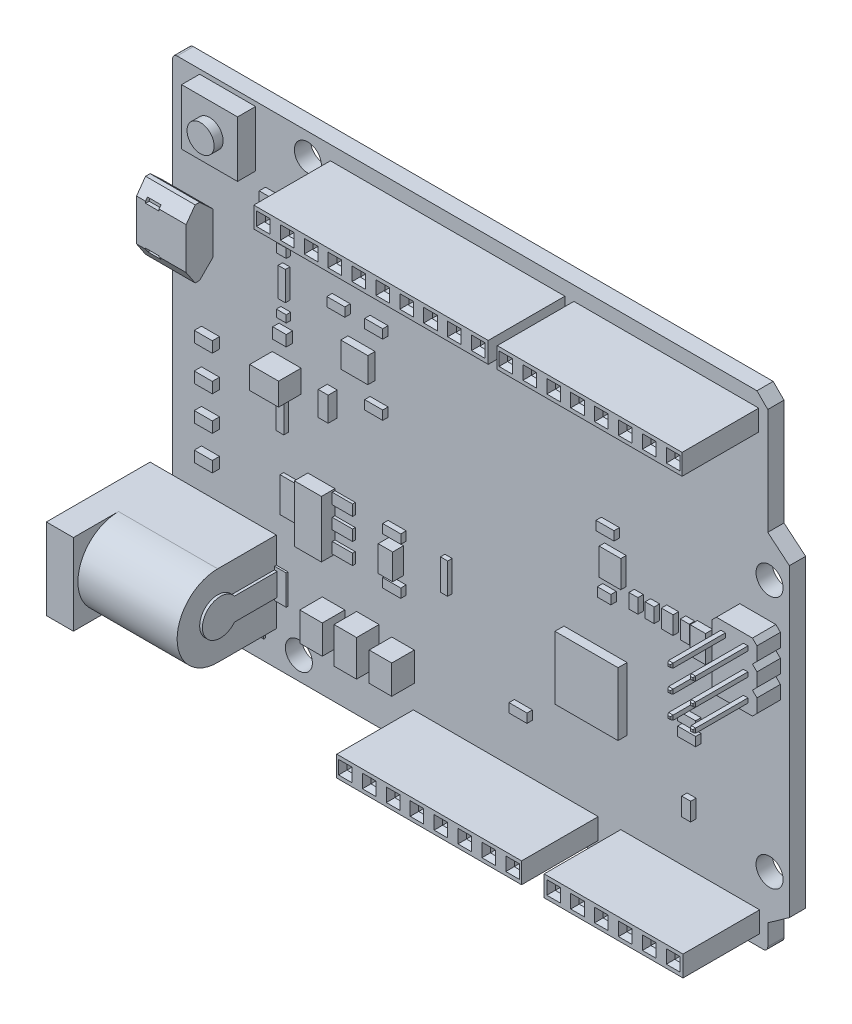
SolidWorks part; units mm, degrees
ref_plane "Front Plane" through (0, 0, 0) normal (0, 0, 1) x (1, 0, 0)
ref_plane "Top Plane" through (0, 0, 0) normal (0, 1, 0) x (1, 0, 0)
ref_plane "Right Plane" through (0, 0, 0) normal (1, 0, 0) x (0, 0, -1)
sketch "Sketch1" plane through (0, 0, 0) normal (0, 0, 1) x (1, 0, 0)
  line L0 (66, -1.2) -> (66, -13)
  line L1 (0.5, 0) -> (64.8, 0)
  line L2 (0, -0.5) -> (0, -52.8)
  line L3 (0.5, -53.3) -> (65.5, -53.3)
  line L4 (68.4, -15) -> (68.4, -48.8)
  line L5 (66, -13) -> (68.4, -15)
  line L6 (68.4, -48.8) -> (66, -50.5)
  line L7 (66, -50.5) -> (66, -52.8)
  line L8 (64.8, 0) -> (66, -1.2)
  arc A0 (65.5, -53.3) -> (66, -52.8) centre (65.5, -52.8) ccw
  arc A1 (0, -52.8) -> (0.5, -53.3) centre (0.5, -52.8) ccw
  arc A2 (0.5, 0) -> (0, -0.5) centre (0.5, -0.5) ccw
  point P12 (66, -53.3)
  point P15 (0, -53.3)
  point P18 (0, 0)
  dimension "D5" = 0.5
  dimension "D1" = 68.4
  dimension "D2" = 53.3
  dimension "D3" = 66
  dimension "D4" = 66
  dimension "D6" = 15
  dimension "D7" = 48.8
  dimension "D8" = 50.5
  dimension "D9" = 45
  dimension "D10" = 1.2
extrude "Boss-Extrude1" add sketch "Sketch1" along normal blind 1.8
sketch "Sketch2" plane through (0, 0, 1.8) normal (0, 0, 1) x (1, 0, 0)
  line L0 (0, -0.5) -> (0, -52.8) construction
  line L1 (64.8, 0) -> (0.5, 0) construction
  line L2 (68.4, -48.8) -> (68.4, -15) construction
  line L3 (0.5, -53.3) -> (65.5, -53.3) construction
  point P0 (15, -2.5)
  point P1 (66.2, -17.5)
  point P2 (66.2, -45.5)
  point P3 (14, -50.8)
  dimension "D1" = 15
  dimension "D2" = 2.5
  dimension "D3" = 2.2
  dimension "D4" = 2.2
  dimension "D5" = 2.5
  dimension "D6" = 14
  dimension "D7" = 17.5
  dimension "D8" = 45.5
hole_wizard "Ø3.0 (3) Diameter Hole2" positions "Sketch6" profile "Sketch7" hole size "Ø3.0" standard "ISO" end condition through all
sketch "Sketch6" plane through (0, 0, 1.8) normal (0, 0, 1) x (1, 0, 0)
  point P0 (15, -2.5)
  point P3 (66.2, -17.5)
  point P6 (66.2, -45.5)
  point P9 (14, -50.8)
sketch "Sketch7" plane through (15, -2.5, 1.8) normal (1, 0, 0) x (0, -1, 0)
  line L0 (0, 0) -> (0, 1.8)
  line L1 (0, 1.8) -> (1.5, 1.8)
  line L2 (1.5, 1.8) -> (1.5, 0)
  line L5 (1.5, 0) -> (0, 0)
  line L11 (0, -6.35) -> (0, 107.95) construction
  dimension "Thru Hole Dia." = 3
  dimension "Thru Hole Depth" = 1.8
sketch "Sketch8" plane through (0, 0, 1.8) normal (0, 0, 1) x (1, 0, 0)
  line L0 (0.5, -53.3) -> (65.5, -53.3) construction
  line L1 (44.5, -1.5683) -> (65, -1.5683)
  line L2 (44.5, -1.5683) -> (44.5, -3.8683)
  line L3 (44.5, -3.8683) -> (65, -3.8683)
  line L4 (65, -1.5683) -> (65, -3.8683)
  line L5 (17.5, -1.5683) -> (43.5, -1.5683)
  line L6 (17.5, -1.5683) -> (17.5, -3.8683)
  line L7 (17.5, -3.8683) -> (43.5, -3.8683)
  line L8 (43.5, -1.5683) -> (43.5, -3.8683)
  line L9 (65.1, -52) -> (49.7, -52)
  line L10 (65.1, -52) -> (65.1, -49.7)
  line L11 (65.1, -49.7) -> (49.7, -49.7)
  line L12 (49.7, -52) -> (49.7, -49.7)
  line L13 (47.2, -52) -> (26.7, -52)
  line L14 (47.2, -52) -> (47.2, -49.7)
  line L15 (47.2, -49.7) -> (26.7, -49.7)
  line L16 (26.7, -52) -> (26.7, -49.7)
  line L17 (68.4, -48.8) -> (68.4, -15) construction
  line L18 (66, -13) -> (66, -1.2) construction
  dimension "D1" = 2.3
  dimension "D2" = 2.3
  dimension "D3" = 2.3
  dimension "D4" = 2.3
  dimension "D5" = 15.4
  dimension "D6" = 1.3
  dimension "D7" = 1.3
  dimension "D8" = 20.5
  dimension "D9" = 2.5
  dimension "D10" = 3.3
  dimension "D11" = 1
  dimension "D12" = 1
  dimension "D13" = 20.5
  dimension "D14" = 26
extrude "Boss-Extrude2" add sketch "Sketch8" along normal blind 8.5
sketch "Sketch10" plane through (0, 0, 10.3) normal (0, 0, 1) x (1, 0, 0)
  line L0 (26.7, -49.7) -> (26.7, -52) construction
  line L1 (26.9, -50.1) -> (28.4, -50.1)
  line L2 (26.9, -50.1) -> (26.9, -51.6)
  line L3 (26.9, -51.6) -> (28.4, -51.6)
  line L4 (28.4, -50.1) -> (28.4, -51.6)
  line L5 (26.7, -52) -> (47.2, -52) construction
  dimension "D1" = 1.5
  dimension "D2" = 1.5
  dimension "D3" = 0.2
  dimension "D4" = 0.4
extrude "Cut-Extrude1" cut sketch "Sketch10" against normal blind 8.5 draft 20
sketch "Sketch11" plane through (0, 0, 10.3) normal (0, 0, 1) x (1, 0, 0)
  line L0 (27.65, -50.85) -> (28.4, -51.6) construction
  line L1 (27.15, -50.35) -> (28.15, -50.35)
  line L2 (27.15, -50.35) -> (27.15, -51.35)
  line L3 (27.15, -51.35) -> (28.15, -51.35)
  line L4 (28.15, -50.35) -> (28.15, -51.35)
  line L5 (27.15, -50.35) -> (28.15, -51.35) construction
  line L6 (27.15, -51.35) -> (28.15, -50.35) construction
  point P0 (27.65, -50.85)
  dimension "D1" = 1
  dimension "D2" = 1
extrude "Cut-Extrude2" cut sketch "Sketch11" against normal blind 8.5
pattern_linear "LPattern1" count 8 spacing 2.65 along (1, 0, 0) of "Cut-Extrude2", "Cut-Extrude1"
sketch "Sketch12" plane through (0, 0, 10.3) normal (0, 0, 1) x (1, 0, 0)
  line L0 (65.1, -49.7) -> (49.7, -49.7) construction
  line L1 (50, -50.1) -> (51.5, -50.1)
  line L2 (50, -50.1) -> (50, -51.6)
  line L3 (50, -51.6) -> (51.5, -51.6)
  line L4 (51.5, -50.1) -> (51.5, -51.6)
  line L5 (49.7, -49.7) -> (49.7, -52) construction
  dimension "D1" = 1.5
  dimension "D2" = 1.5
  dimension "D3" = 0.4
  dimension "D4" = 0.3
extrude "Cut-Extrude3" cut sketch "Sketch12" against normal blind 8.5 draft 20
sketch "Sketch14" plane through (0, 0, 10.3) normal (0, 0, 1) x (1, 0, 0)
  line L0 (50.75, -50.85) -> (51.5, -50.1) construction
  line L1 (50.25, -50.35) -> (51.25, -50.35)
  line L2 (50.25, -50.35) -> (50.25, -51.35)
  line L3 (50.25, -51.35) -> (51.25, -51.35)
  line L4 (51.25, -50.35) -> (51.25, -51.35)
  line L5 (50.25, -50.35) -> (51.25, -51.35) construction
  line L6 (50.25, -51.35) -> (51.25, -50.35) construction
  line L7 (50.75, -50.85) -> (50, -51.6) construction
  line L8 (51.5, -50.1) -> (50, -50.1) construction
  line L9 (50, -50.1) -> (50, -51.6) construction
  point P0 (50.75, -50.85)
  dimension "D1" = 1
  dimension "D2" = 1
  dimension "D3" = 0.25
  dimension "D4" = 0.25
extrude "Cut-Extrude4" cut sketch "Sketch14" against normal blind 8.5
pattern_linear "LPattern2" count 6 spacing 2.65 along (1, 0, 0) of "Cut-Extrude4", "Cut-Extrude3"
sketch "Sketch15" plane through (0, 0, 10.3) normal (0, 0, 1) x (1, 0, 0)
  line L0 (17.5, -1.5683) -> (17.5, -3.8683) construction
  line L1 (17.8, -1.9683) -> (19.3, -1.9683)
  line L2 (17.8, -1.9683) -> (17.8, -3.4683)
  line L3 (17.8, -3.4683) -> (19.3, -3.4683)
  line L4 (19.3, -1.9683) -> (19.3, -3.4683)
  line L5 (43.5, -1.5683) -> (17.5, -1.5683) construction
  point P4 (17.5, -2.7183)
  dimension "D1" = 0.3
  dimension "D2" = 1.5
  dimension "D3" = 0.4
  dimension "D4" = 1.5
extrude "Cut-Extrude5" cut sketch "Sketch15" against normal blind 8.5 draft 20
sketch "Sketch16" plane through (0, 0, 10.3) normal (0, 0, 1) x (1, 0, 0)
  line L0 (18.55, -2.7183) -> (19.3, -3.4683) construction
  line L1 (18.0652, -2.2335) -> (19.0652, -2.2335)
  line L2 (18.0652, -2.2335) -> (18.0652, -3.2335)
  line L3 (18.0652, -3.2335) -> (19.0652, -3.2335)
  line L4 (19.0652, -2.2335) -> (19.0652, -3.2335)
  line L5 (18.0652, -2.2335) -> (19.0652, -3.2335) construction
  line L6 (18.0652, -3.2335) -> (19.0652, -2.2335) construction
  point P0 (18.5652, -2.7335)
  dimension "D1" = 1
extrude "Cut-Extrude6" cut sketch "Sketch16" against normal blind 8.5
pattern_linear "LPattern3" count 10 spacing 2.65 along (1, 0, 0) of "Cut-Extrude5", "Cut-Extrude6"
sketch "Sketch17" plane through (0, 0, 10.3) normal (0, 0, 1) x (1, 0, 0)
  line L0 (65, -1.5683) -> (44.5, -1.5683) construction
  line L1 (44.7, -1.9683) -> (46.2, -1.9683)
  line L2 (44.7, -1.9683) -> (44.7, -3.4683)
  line L3 (44.7, -3.4683) -> (46.2, -3.4683)
  line L4 (46.2, -1.9683) -> (46.2, -3.4683)
  line L5 (44.5, -1.5683) -> (44.5, -3.8683) construction
  dimension "D1" = 0.4
  dimension "D2" = 1.5
  dimension "D3" = 1.5
  dimension "D4" = 0.2
extrude "Cut-Extrude7" cut sketch "Sketch17" against normal blind 8.5 draft 20
sketch "Sketch18" plane through (0, 0, 10.3) normal (0, 0, 1) x (1, 0, 0)
  line L0 (45.45, -2.7183) -> (46.2, -3.4683) construction
  line L1 (44.95, -2.2183) -> (45.95, -2.2183)
  line L2 (44.95, -2.2183) -> (44.95, -3.2183)
  line L3 (44.95, -3.2183) -> (45.95, -3.2183)
  line L4 (45.95, -2.2183) -> (45.95, -3.2183)
  line L5 (44.95, -2.2183) -> (45.95, -3.2183) construction
  line L6 (44.95, -3.2183) -> (45.95, -2.2183) construction
  point P0 (45.45, -2.7183)
  dimension "D1" = 1
extrude "Cut-Extrude8" cut sketch "Sketch18" against normal blind 8.5
pattern_linear "LPattern4" count 8 spacing 2.65 along (1, 0, 0) of "Cut-Extrude8", "Cut-Extrude7"
sketch "Sketch19" plane through (0, 0, 1.8) normal (0, 0, 1) x (1, 0, 0)
  line L0 (68.4, -48.8) -> (68.4, -15) construction
  line L1 (62.4, -21.4) -> (67.4, -21.4)
  line L2 (62.4, -21.4) -> (62.4, -23.4)
  line L3 (62.4, -28.9) -> (67.4, -28.9)
  line L4 (67.4, -21.4) -> (67.4, -23.4)
  line L5 (64.8, 0) -> (0.5, 0) construction
  line L6 (66.9, -26.4) -> (67.4, -25.9)
  line L7 (66.9, -26.4) -> (67.4, -26.9)
  line L10 (62.9, -26.4) -> (62.4, -26.9)
  line L11 (62.9, -26.4) -> (62.4, -25.9)
  line L12 (66.9, -23.9) -> (67.4, -23.4)
  line L13 (66.9, -23.9) -> (67.4, -24.4)
  line L14 (62.9, -23.9) -> (62.4, -24.4)
  line L15 (62.9, -23.9) -> (62.4, -23.4)
  line L16 (62.4, -24.4) -> (62.4, -25.9)
  line L17 (62.4, -26.9) -> (62.4, -28.9)
  line L18 (67.4, -24.4) -> (67.4, -25.9)
  line L19 (67.4, -26.9) -> (67.4, -28.9)
  dimension "D1" = 5
  dimension "D2" = 7.5
  dimension "D3" = 5
  dimension "D4" = 1
  dimension "D5" = 21.4
  dimension "D6" = 2.5
  dimension "D7" = 5
  dimension "D8" = 90
  dimension "D9" = 135
  dimension "D10" = 135
  dimension "D11" = 90
  dimension "D12" = 90
  dimension "D13" = 90
  dimension "D14" = 135
  dimension "D15" = 135
  dimension "D16" = 0.5
  dimension "D17" = 0.5
  dimension "D18" = 0.5
  dimension "D19" = 0.5
extrude "Boss-Extrude3" add sketch "Sketch19" along normal blind 2.6
chamfer "Chamfer1" distance 0.5 angle 45 4 edges at (62.4, -21.4, 3.1) (62.4, -28.9, 3.1) (67.4, -28.9, 3.1) (67.4, -21.4, 3.1)
sketch "Sketch20" plane through (0, 0, 4.4) normal (0, 0, 1) x (1, 0, 0)
  line L0 (66.9, -21.4) -> (62.9, -21.4) construction
  line L1 (63.4, -22.4) -> (63.9, -22.4)
  line L2 (63.4, -22.4) -> (63.4, -22.9)
  line L3 (63.4, -22.9) -> (63.9, -22.9)
  line L4 (63.9, -22.4) -> (63.9, -22.9)
  line L5 (65.9, -22.4) -> (66.4, -22.4)
  line L6 (65.9, -22.4) -> (65.9, -22.9)
  line L7 (65.9, -22.9) -> (66.4, -22.9)
  line L8 (66.4, -22.4) -> (66.4, -22.9)
  line L9 (62.4, -21.9) -> (62.4, -23.4) construction
  line L10 (67.4, -23.4) -> (67.4, -21.9) construction
  point P11 (62.4, -22.65)
  dimension "D1" = 0.5
  dimension "D2" = 0.5
  dimension "D3" = 0.5
  dimension "D4" = 0.5
  dimension "D5" = 2
  dimension "D6" = 1
  dimension "D7" = 1
  dimension "D8" = 1
  dimension "D9" = 1
  dimension "D10" = 1
extrude "Boss-Extrude4" add sketch "Sketch20" along normal blind 6
chamfer "Chamfer2" distance 0.2 angle 30 8 edges at (66.4, -22.65, 10.4) (66.15, -22.9, 10.4) (65.9, -22.65, 10.4) (66.15, -22.4, 10.4) (63.9, -22.65, 10.4) (63.65, -22.4, 10.4) (63.4, -22.65, 10.4) (63.65, -22.9, 10.4) first distance on face at (66.4, -22.65, 7.4) first distance on face at (66.15, -22.9, 7.4) first distance on face at (65.9, -22.65, 7.4) first distance on face at (66.15, -22.4, 7.4) first distance on face at (63.9, -22.65, 7.4) first distance on face at (63.65, -22.4, 7.4) first distance on face at (63.4, -22.65, 7.4) first distance on face at (63.65, -22.9, 7.4)
pattern_linear "LPattern6" count 3 spacing 2.5 along (0, -1, 0) of "Chamfer2", "Boss-Extrude4"
sketch "Sketch21" plane through (0, 0, 1.8) normal (0, 0, 1) x (1, 0, 0)
  line L0 (68.4, -48.8) -> (68.4, -15) construction
  line L1 (43.4, -33.3) -> (50.4, -33.3)
  line L2 (43.4, -33.3) -> (43.4, -40.3)
  line L3 (43.4, -40.3) -> (50.4, -40.3)
  line L4 (50.4, -33.3) -> (50.4, -40.3)
  line L5 (0.5, -53.3) -> (65.5, -53.3) construction
  dimension "D1" = 7
  dimension "D2" = 7
  dimension "D3" = 18
  dimension "D4" = 20
extrude "Boss-Extrude5" add sketch "Sketch21" along normal blind 1
sketch "Sketch22" plane through (0, 0, 1.8) normal (0, 0, 1) x (1, 0, 0)
  line L0 (62.4, -26.9) -> (62.4, -28.4) construction
  line L1 (58.2, -25.3683) -> (59.9, -25.3683)
  line L2 (58.2, -25.3683) -> (58.2, -28.3683)
  line L3 (58.2, -28.3683) -> (59.9, -28.3683)
  line L4 (59.9, -25.3683) -> (59.9, -28.3683)
  line L5 (44.5, -3.8683) -> (65, -3.8683) construction
  point P4 (62.4, -27.65)
  dimension "D1" = 3
  dimension "D2" = 1.7
  dimension "D3" = 2.5
  dimension "D4" = 21.5
extrude "Boss-Extrude6" add sketch "Sketch22" along normal blind 0.8
sketch "Sketch23" plane through (0, 0, 1.8) normal (0, 0, 1) x (1, 0, 0)
  line L0 (58.2, -25.3683) -> (58.2, -28.3683) construction
  line L1 (56.9, -25.5683) -> (57.9, -25.5683)
  line L2 (56.9, -25.5683) -> (56.9, -27.5683)
  line L3 (56.9, -27.5683) -> (57.9, -27.5683)
  line L4 (57.9, -25.5683) -> (57.9, -27.5683)
  line L5 (54.8, -25.5683) -> (56.1, -25.5683)
  line L6 (54.8, -25.5683) -> (54.8, -27.5683)
  line L7 (54.8, -27.5683) -> (56.1, -27.5683)
  line L8 (56.1, -25.5683) -> (56.1, -27.5683)
  line L10 (53, -25.8683) -> (54, -25.8683)
  line L11 (53, -25.8683) -> (53, -27.4683)
  line L12 (53, -27.4683) -> (54, -27.4683)
  line L13 (51.2, -25.8683) -> (52.2, -25.8683)
  line L14 (51.2, -25.8683) -> (51.2, -27.4683)
  line L15 (51.2, -27.4683) -> (52.2, -27.4683)
  line L16 (52.2, -25.8683) -> (52.2, -27.4683)
  line L17 (47.9, -23.0683) -> (50.3, -23.0683)
  line L18 (47.9, -23.0683) -> (47.9, -26.0683)
  line L19 (47.9, -26.0683) -> (50.3, -26.0683)
  line L20 (50.3, -23.0683) -> (50.3, -26.0683)
  line L21 (47.5517, -20.7683) -> (49.5517, -20.7683)
  line L22 (47.5517, -20.7683) -> (47.5517, -21.7683)
  line L23 (47.5517, -21.7683) -> (49.5517, -21.7683)
  line L24 (49.5517, -20.7683) -> (49.5517, -21.7683)
  line L25 (47.7, -27.0683) -> (49.2, -27.0683)
  line L26 (47.7, -27.0683) -> (47.7, -28.0683)
  line L27 (47.7, -28.0683) -> (49.2, -28.0683)
  line L28 (49.2, -27.0683) -> (49.2, -28.0683)
  line L29 (59.9, -25.3683) -> (58.2, -25.3683) construction
  line L30 (54, -25.8683) -> (54, -27.4683)
  dimension "D1" = 0.3
  dimension "D2" = 1
  dimension "D3" = 1.3
  dimension "D4" = 1
  dimension "D5" = 1
  dimension "D6" = 0.2
  dimension "D7" = 0.8
  dimension "D8" = 0.8
  dimension "D9" = 0.8
  dimension "D10" = 0.3
  dimension "D11" = 1.6
  dimension "D12" = 1.6
  dimension "D13" = 0.3
  dimension "D14" = 2
  dimension "D15" = 2
  dimension "D16" = 2.4
  dimension "D17" = 0.9
  dimension "D18" = 3
  dimension "D19" = 0.2
  dimension "D20" = 1
  dimension "D21" = 1.5
  dimension "D22" = 2
  dimension "D23" = 1
  dimension "D24" = 2
  dimension "D25" = 1.3
  dimension "D26" = 1
extrude "Boss-Extrude7" add sketch "Sketch23" along normal blind 0.6
sketch "Sketch24" plane through (0, 0, 1.8) normal (0, 0, 1) x (1, 0, 0)
  line L0 (65.1, -49.7) -> (49.7, -49.7) construction
  line L1 (56.6, -34.5) -> (58.6, -34.5)
  line L2 (56.6, -34.5) -> (56.6, -35.5)
  line L3 (56.6, -35.5) -> (58.6, -35.5)
  line L4 (58.6, -34.5) -> (58.6, -35.5)
  line L5 (56.6, -36) -> (58.6, -36)
  line L6 (56.6, -36) -> (56.6, -37)
  line L7 (56.6, -37) -> (58.6, -37)
  line L8 (58.6, -36) -> (58.6, -37)
  line L9 (57.0515, -42.5) -> (58.0515, -42.5)
  line L10 (57.0515, -42.5) -> (57.0515, -44.5)
  line L11 (57.0515, -44.5) -> (58.0515, -44.5)
  line L12 (58.0515, -42.5) -> (58.0515, -44.5)
  line L13 (37.9, -43.1) -> (39.9, -43.1)
  line L14 (37.9, -43.1) -> (37.9, -44.1)
  line L15 (37.9, -44.1) -> (39.9, -44.1)
  line L16 (39.9, -43.1) -> (39.9, -44.1)
  line L17 (21.9, -22) -> (23.9, -22)
  line L18 (21.9, -22) -> (21.9, -23)
  line L19 (21.9, -23) -> (23.9, -23)
  line L20 (23.9, -22) -> (23.9, -23)
  line L21 (23.9, -32.9) -> (25.9, -32.9)
  line L22 (23.9, -32.9) -> (23.9, -33.9)
  line L23 (23.9, -33.9) -> (25.9, -33.9)
  line L24 (25.9, -32.9) -> (25.9, -33.9)
  line L25 (23.9, -38.1) -> (25.9, -38.1)
  line L26 (23.9, -38.1) -> (23.9, -39.1)
  line L27 (23.9, -39.1) -> (25.9, -39.1)
  line L28 (25.9, -38.1) -> (25.9, -39.1)
  line L29 (50.4, -40.3) -> (50.4, -33.3) construction
  line L30 (43.4, -33.3) -> (43.4, -40.3) construction
  line L31 (47.2, -49.7) -> (26.7, -49.7) construction
  line L33 (43.4, -33.3) -> (43.4, -40.3) construction
  line L34 (17.7, -14.2) -> (19.7, -14.2)
  line L35 (17.7, -14.2) -> (17.7, -15.2)
  line L36 (17.7, -15.2) -> (19.7, -15.2)
  line L37 (19.7, -14.2) -> (19.7, -15.2)
  line L38 (21.9, -14.2) -> (23.9, -14.2)
  line L39 (21.9, -14.2) -> (21.9, -15.2)
  line L40 (21.9, -15.2) -> (23.9, -15.2)
  line L41 (23.9, -14.2) -> (23.9, -15.2)
  dimension "D1" = 1
  dimension "D2" = 1
  dimension "D3" = 2
  dimension "D4" = 2
  dimension "D5" = 1
  dimension "D6" = 2
  dimension "D7" = 1
  dimension "D8" = 1
  dimension "D9" = 2
  dimension "D10" = 2
  dimension "D11" = 2
  dimension "D12" = 1
  dimension "D13" = 2
  dimension "D14" = 1
  dimension "D15" = 5.2
  dimension "D16" = 5.5
  dimension "D17" = 0.5
  dimension "D18" = 6.2
  dimension "D19" = 3.5
  dimension "D20" = 5.6
  dimension "D21" = 10.6
  dimension "D22" = 4.2
  dimension "D23" = 17.5
  dimension "D24" = 19.5
  dimension "D25" = 9.9
  dimension "D26" = 2
  dimension "D27" = 2
  dimension "D28" = 2.2
  dimension "D29" = 19.5
  dimension "D30" = 6.8
  dimension "D31" = 6.8
  dimension "D32" = 1
  dimension "D33" = 1
  dimension "D34" = 17.5
extrude "Boss-Extrude8" add sketch "Sketch24" along normal blind 0.6
sketch "Sketch25" plane through (0, 0, 1.8) normal (0, 0, 1) x (1, 0, 0)
  line L0 (17.7, -15.2) -> (19.7, -15.2) construction
  line L1 (19.45, -17.4) -> (22.45, -17.4)
  line L2 (19.45, -17.4) -> (19.45, -20.2)
  line L3 (19.45, -20.2) -> (22.45, -20.2)
  line L4 (22.45, -17.4) -> (22.45, -20.2)
  line L5 (23.9, -23) -> (23.9, -22) construction
  dimension "D1" = 2.2
  dimension "D2" = 2.8
  dimension "D3" = 3
  dimension "D4" = 1.45
extrude "Boss-Extrude9" add sketch "Sketch25" along normal blind 0.8
sketch "Sketch26" plane through (0, 0, 1.8) normal (0, 0, 1) x (1, 0, 0)
  line L0 (25.9, -38.1) -> (23.9, -38.1) construction
  line L1 (24, -34.4854) -> (25.6, -34.4854)
  line L2 (24, -34.4854) -> (24, -37.35)
  line L3 (24, -37.35) -> (25.6, -37.35)
  line L4 (25.6, -34.4854) -> (25.6, -37.35)
  line L5 (43.4, -33.3) -> (43.4, -40.3) construction
  dimension "D1" = 1.6
  dimension "D2" = 2.8646
  dimension "D3" = 0.75
  dimension "D4" = 17.8
extrude "Boss-Extrude10" add sketch "Sketch26" along normal blind 1.2
sketch "Sketch27" plane through (0, 0, 1.8) normal (0, 0, 1) x (1, 0, 0)
  line L0 (43.4, -33.3) -> (43.4, -40.3) construction
  line L1 (24.3, -44.5) -> (26.8, -44.5)
  line L2 (24.3, -44.5) -> (24.3, -46.5)
  line L3 (24.3, -46.5) -> (26.8, -46.5)
  line L4 (26.8, -44.5) -> (26.8, -46.5)
  line L5 (16.6, -44.5) -> (19.1, -44.5)
  line L6 (16.6, -44.5) -> (16.6, -46.5)
  line L7 (16.6, -46.5) -> (19.1, -46.5)
  line L8 (19.1, -44.5) -> (19.1, -46.5)
  line L9 (20.4, -43.4) -> (22.9, -43.4)
  line L10 (20.4, -43.4) -> (20.4, -47.4)
  line L11 (20.4, -47.4) -> (22.9, -47.4)
  line L12 (22.9, -43.4) -> (22.9, -47.4)
  line L13 (47.2, -49.7) -> (26.7, -49.7) construction
  line L14 (47.2, -49.7) -> (26.7, -49.7) construction
  dimension "D1" = 2.5
  dimension "D2" = 2.5
  dimension "D3" = 2
  dimension "D4" = 2
  dimension "D5" = 16.6
  dimension "D6" = 5.2
  dimension "D7" = 3.2
  dimension "D8" = 2.3
  dimension "D9" = 2.5
  dimension "D10" = 4
  dimension "D11" = 1.4
extrude "Boss-Extrude11" add sketch "Sketch27" along normal blind 2.5
sketch "Sketch28" plane through (0, 0, 1.8) normal (0, 0, 1) x (1, 0, 0)
  line L1 (24.3, -44.5) -> (26.8, -44.5)
  line L2 (24.3, -44.5) -> (24.3, -43.9)
  line L3 (24.3, -43.9) -> (26.8, -43.9)
  line L4 (26.8, -44.5) -> (26.8, -43.9)
  line L5 (24.3, -46.5) -> (26.8, -46.5)
  line L6 (24.3, -46.5) -> (24.3, -47.1)
  line L7 (24.3, -47.1) -> (26.8, -47.1)
  line L8 (26.8, -46.5) -> (26.8, -47.1)
  line L9 (19.1, -46.5) -> (16.6, -46.5)
  line L10 (19.1, -46.5) -> (19.1, -47.1)
  line L11 (19.1, -47.1) -> (16.6, -47.1)
  line L12 (16.6, -46.5) -> (16.6, -47.1)
  line L13 (16.6, -44.5) -> (19.1, -44.5)
  line L14 (16.6, -44.5) -> (16.6, -43.9)
  line L15 (16.6, -43.9) -> (19.1, -43.9)
  line L16 (19.1, -44.5) -> (19.1, -43.9)
  dimension "D1" = 0.6
  dimension "D2" = 0.6
  dimension "D5" = 0.6
  dimension "D6" = 0.6
extrude "Boss-Extrude12" add sketch "Sketch28" along normal blind 2.5
sketch "Sketch30" plane through (0, 0, 1.8) normal (0, 0, 1) x (1, 0, 0)
  line L0 (0.5, -53.3) -> (65.5, -53.3) construction
  line L1 (11.5, -40.5) -> (-2.5, -40.5)
  line L2 (11.5, -40.5) -> (11.5, -49.5)
  line L3 (11.5, -49.5) -> (-2.5, -49.5)
  line L4 (-2.5, -40.5) -> (-2.5, -49.5)
  line L5 (0, -0.5) -> (0, -52.8) construction
  dimension "D1" = 14
  dimension "D2" = 9
  dimension "D3" = 3.8
  dimension "D4" = 2.5
extrude "Boss-Extrude13" add sketch "Sketch30" along normal blind 6.5
sketch "Sketch31" plane through (-2.5, 0, 0) normal (-1, 0, 0) x (0, 0, 1)
  line L0 (8.3, -40.5) -> (8.3, -49.5) construction
  circle A0 centre (8.3, -45) radius 4.5
  dimension "D1" = 9
extrude "Boss-Extrude14" add sketch "Sketch31" against normal blind 14
sketch "Sketch32" plane through (-2.5, 0, 0) normal (-1, 0, 0) x (0, 0, 1)
  line L1 (8.3, -40.5) -> (13.3, -40.5)
  line L2 (8.3, -40.5) -> (8.3, -49.5)
  line L3 (8.3, -49.5) -> (13.3, -49.5)
  line L4 (13.3, -40.5) -> (13.3, -49.5)
  dimension "D1" = 5
extrude "Boss-Extrude15" add sketch "Sketch32" against normal blind 3
sketch "Sketch33" plane through (-2.5, 0, 0) normal (-1, 0, 0) x (0, 0, 1)
  line L0 (13.3, -49.5) -> (1.8, -49.5) construction
  line L1 (13.3, -49.5) -> (13.3, -40.5) construction
  circle A0 centre (8.3, -45) radius 2.8159
  dimension "D1" = 4.5
  dimension "D2" = 5
extrude "Cut-Extrude9" cut sketch "Sketch33" against normal blind 10
sketch "Sketch34" plane through (7.5, 0, 0) normal (-1, 0, 0) x (0, 0, 1)
  circle A0 centre (8.3, -45) radius 1.25
  dimension "D1" = 2.5
extrude "Boss-Extrude16" add sketch "Sketch34" along normal blind 9
fillet "Fillet1" radius 1.25 1 edges at (-1.5, -46.25, 8.3)
sketch "Sketch35" plane through (0, -49.5, 0) normal (0, -1, 0) x (1, 0, 0)
  line L0 (0, 1.8) -> (11.5, 1.8) construction
  line L1 (7.5, 1.8) -> (10, 1.8)
  line L2 (7.5, 1.8) -> (7.5, 6.3)
  line L3 (7.5, 6.3) -> (10, 6.3)
  line L4 (10, 1.8) -> (10, 6.3)
  line L5 (11.5, 8.3) -> (11.5, 1.8) construction
  dimension "D1" = 2.5
  dimension "D2" = 4.5
  dimension "D3" = 1.5
extrude "Boss-Extrude17" add sketch "Sketch35" along normal blind 0.2
sketch "Sketch36" plane through (11.5, 0, 0) normal (1, 0, 0) x (0, 0, -1)
  line L0 (-1.8, -49.5) -> (-1.8, -40.5) construction
  line L1 (-6.7388, -46.25) -> (-1.8, -46.25)
  line L3 (-6.7388, -43.75) -> (-1.8, -43.75)
  line L4 (-1.8, -46.25) -> (-1.8, -43.75)
  line L5 (-8.3, -40.5) -> (-1.8, -40.5) construction
  line L6 (-1.8, -49.5) -> (-6.3, -49.5) construction
  arc A0 (-6.7388, -43.75) -> (-6.7388, -46.25) centre (-8.3, -45) ccw
  dimension "D2" = 4
  dimension "D1" = 2.5
  dimension "D3" = 3.25
  dimension "D4" = 3.25
extrude "Boss-Extrude18" add sketch "Sketch36" along normal blind 0.3
sketch "Sketch37" plane through (0, 0, 0) normal (-1, 0, 0) x (0, 0, 1)
  line L0 (1.8, -12.7) -> (3.3, -11.3)
  line L2 (1.8, -0.5) -> (1.8, -40.5) construction
  line L3 (3.3, -11.3) -> (3.8, -11.3)
  line L4 (3.8, -11.3) -> (4.8, -12.7)
  line L5 (4.8, -12.7) -> (4.8, -17.3)
  line L6 (3.3, -11.3) -> (3.3, -18.8)
  line L7 (3.3, -18.8) -> (1.8, -17.3)
  line L8 (3.3, -18.8) -> (3.8, -18.8)
  line L9 (3.8, -18.8) -> (4.8, -17.3)
  line L10 (1.8, -12.7) -> (1.8, -17.3)
  line L11 (3.4577, -11.7) -> (3.5942, -11.7)
  line L12 (3.5942, -11.7) -> (4.4, -12.8282)
  line L13 (4.4, -12.8282) -> (4.4, -17.1789)
  line L14 (3.5859, -18.4) -> (4.4, -17.1789)
  line L15 (3.4657, -18.4) -> (3.5859, -18.4)
  line L16 (3.4657, -18.4) -> (2.2, -17.1343)
  line L17 (2.2, -12.8738) -> (2.2, -17.1343)
  line L18 (2.2, -12.8738) -> (3.4577, -11.7)
  line L19 (1.8, 0) -> (0, 0) construction
  line L20 (2.2, -12.8738) -> (3.5729, -11.5924) construction
  line L21 (3.3, -11.7) -> (3.5942, -11.7) construction
  line L22 (3.3, -18.4) -> (3.5859, -18.4) construction
  line L23 (3.5828, -18.5172) -> (2.2, -17.1343) construction
  line M5 (1.8, -40.5) -> (1.8, -0.5)
  dimension "D1" = 3
  dimension "D2" = 1.5
  dimension "D3" = 0.5
  dimension "D4" = 7.5
  dimension "D5" = 1.4
  dimension "D6" = 0.4
  dimension "D7" = 11.3
extrude "Boss-Extrude19" add sketch "Sketch37" against normal blind 4.5 and the other way blind 1 contours L6 L18 L11 L12 L13 L14 L15 L16 L8 L9 L5 L4 L3 | L17 L18 L6 L0 L7 L16 M5 region at (0, -12.0559, 2.6022) region at (0, -11.3765, 3.55)
sketch "Sketch38" plane through (4.5, 0, 0) normal (1, 0, 0) x (0, 0, -1)
  line L0 (-4.4, -12.8282) -> (-4.4, -17.1789)
  line L1 (-4.4, -17.1789) -> (-3.5921, -18.5321)
  line L2 (-3.5921, -18.5321) -> (-3.2472, -18.5321)
  line L3 (-3.2472, -18.5321) -> (-1.9826, -17.1789)
  line L4 (-1.9826, -17.1789) -> (-1.9826, -12.8282)
  line L5 (-1.9826, -12.8282) -> (-3.4766, -11.5142)
  line L6 (-3.4766, -11.5142) -> (-3.7841, -11.5339)
  line L7 (-3.7841, -11.5339) -> (-4.5864, -12.9086)
  line L8 (-4.5864, -12.9086) -> (-4.4, -17.1789)
  line M1 (-2.2, -12.8738) -> (-2.2, -17.1343)
  line M2 (-2.2, -17.1343) -> (-3.4657, -18.4)
  line M3 (-3.4657, -18.4) -> (-3.5859, -18.4)
  line M4 (-3.5859, -18.4) -> (-4.4, -17.1789)
  line M5 (-4.4, -17.1789) -> (-4.4, -12.8282)
  line M6 (-4.4, -12.8282) -> (-3.5942, -11.7)
  line M7 (-3.5942, -11.7) -> (-3.4577, -11.7)
  line M8 (-3.4577, -11.7) -> (-2.2, -12.8738)
extrude "Boss-Extrude20" add sketch "Sketch38" against normal blind 1 contours M1 M8 M7 M6 M5 M4 M3 M2 region at (4.5, -15.0278, 3.3209)
sketch "Sketch39" plane through (3.5, 0, 0) normal (-1, 0, 0) x (0, 0, 1)
  line L0 (4.4, -12.8282) -> (4.4, -17.1789) construction
  line L1 (3.9, -13.0032) -> (3.4, -13.0032)
  line L2 (3.9, -13.0032) -> (3.9, -17.0032)
  line L3 (3.9, -17.0032) -> (3.4, -17.0032)
  line L4 (3.4, -13.0032) -> (3.4, -17.0032)
  dimension "D1" = 0.5
  dimension "D2" = 0.5
  dimension "D3" = 4
  dimension "D4" = 0.175
  dimension "D5" = 0.1757
extrude "Boss-Extrude21" add sketch "Sketch39" along normal blind 4
sketch "Sketch41" plane through (0, 0, 4.8) normal (0, 0, 1) x (1, 0, 0)
  line L0 (-1, -11.3) -> (4.5, -11.3) construction
  line L1 (0, -12.4) -> (1.5, -12.4)
  line L2 (0, -12.4) -> (0, -12.9)
  line L3 (0, -12.9) -> (1.5, -12.9)
  line L4 (1.5, -12.4) -> (1.5, -12.9)
  line L5 (0, -17.2) -> (1.5, -17.2)
  line L6 (0, -17.2) -> (0, -17.7)
  line L7 (0, -17.7) -> (1.5, -17.7)
  line L8 (1.5, -17.2) -> (1.5, -17.7)
  line L9 (-1, -18.8) -> (4.5, -18.8) construction
  line L10 (-1, -11.3) -> (-1, -12.7) construction
  line L11 (-1, -12.7) -> (-1, -17.3) construction
  dimension "D1" = 1.1
  dimension "D2" = 0.5
  dimension "D3" = 0.5
  dimension "D4" = 1.1
  dimension "D5" = 1.5
  dimension "D6" = 1.5
  dimension "D7" = 1
  dimension "D8" = 1
extrude "Cut-Extrude10" cut sketch "Sketch41" against normal blind 1
sketch "Sketch43" plane through (0, 0, 1.8) normal (0, 0, 1) x (1, 0, 0)
  line L0 (64.8, 0) -> (0.5, 0) construction
  line L1 (3, -0.5) -> (9.2, -0.5)
  line L2 (3, -0.5) -> (3, -6.7)
  line L3 (3, -6.7) -> (9.2, -6.7)
  line L4 (9.2, -0.5) -> (9.2, -6.7)
  line L5 (0, -0.5) -> (0, -12.7) construction
  dimension "D1" = 6.2
  dimension "D2" = 6.2
  dimension "D3" = 0.5
  dimension "D4" = 3
extrude "Boss-Extrude22" add sketch "Sketch43" along normal blind 2
sketch "Sketch44" plane through (0, 0, 3.8) normal (0, 0, 1) x (1, 0, 0)
  line L0 (3, -0.5) -> (3, -6.7) construction
  line L1 (9.2, -0.5) -> (3, -0.5) construction
  circle A0 centre (6.1, -3.6) radius 1.5
  dimension "D3" = 3
  dimension "D1" = 3.1
  dimension "D2" = 3.1
extrude "Boss-Extrude23" add sketch "Sketch44" along normal blind 1
sketch "Sketch45" plane through (0, 0, 1.8) normal (0, 0, 1) x (1, 0, 0)
  line L0 (9.2, -6.7) -> (9.2, -0.5) construction
  line L1 (10.3, -7.7) -> (14.8, -7.7)
  line L2 (10.3, -7.7) -> (10.3, -10.7)
  line L3 (10.3, -10.7) -> (14.8, -10.7)
  line L4 (14.8, -7.7) -> (14.8, -10.7)
  line L5 (3, -6.7) -> (9.2, -6.7) construction
  dimension "D1" = 4.5
  dimension "D2" = 3
  dimension "D3" = 1.1
  dimension "D4" = 1
extrude "Boss-Extrude24" add sketch "Sketch45" along normal blind 0.7
sketch "Sketch46" plane through (0, 0, 1.8) normal (0, 0, 1) x (1, 0, 0)
  line L0 (10.3, -10.7) -> (14.8, -10.7) construction
  line L1 (13.1, -12.9) -> (12, -12.9)
  line L2 (13.1, -12.9) -> (13.1, -11.9)
  line L3 (13.1, -11.9) -> (12, -11.9)
  line L4 (12, -12.9) -> (12, -11.9)
  line L5 (12.2, -14.0036) -> (13, -14.0036)
  line L6 (12.2, -14.0036) -> (12.2, -17.2036)
  line L7 (12.2, -17.2036) -> (13, -17.2036)
  line L8 (13, -14.0036) -> (13, -17.2036)
  line L9 (12, -18.3036) -> (13.1, -18.3036)
  line L10 (12, -18.3036) -> (12, -19.1036)
  line L11 (12, -19.1036) -> (13.1, -19.1036)
  line L12 (13.1, -18.3036) -> (13.1, -19.1036)
  line L13 (14.8, -10.7) -> (14.8, -7.7) construction
  line L17 (11.9692, -26.7892) -> (12.8299, -26.7892)
  line L18 (11.9692, -26.7892) -> (11.9692, -29.9799)
  line L19 (11.9692, -29.9799) -> (12.8299, -29.9799)
  line L20 (12.8299, -26.7892) -> (12.8299, -29.9799)
  dimension "D1" = 1
  dimension "D2" = 1.1
  dimension "D3" = 1.2
  dimension "D4" = 0.8
  dimension "D5" = 3.2
  dimension "D6" = 1.8
  dimension "D7" = 1.7
  dimension "D8" = 1.1
  dimension "D9" = 0.8
  dimension "D10" = 1.1
  dimension "D11" = 0
extrude "Boss-Extrude25" add sketch "Sketch46" along normal blind 0.5
sketch "Sketch47" plane through (0, 0, 1.8) normal (0, 0, 1) x (1, 0, 0)
  line L0 (12, -19.1036) -> (13.1, -19.1036) construction
  line L1 (11.8, -20.0036) -> (13.3, -20.0036)
  line L2 (11.8, -20.0036) -> (11.8, -21.2036)
  line L3 (11.8, -21.2036) -> (13.3, -21.2036)
  line L4 (13.3, -20.0036) -> (13.3, -21.2036)
  line L5 (14.8, -10.7) -> (14.8, -7.7) construction
  dimension "D1" = 1.5
  dimension "D2" = 1.2
  dimension "D3" = 0.9
  dimension "D4" = 1.5
extrude "Boss-Extrude26" add sketch "Sketch47" along normal blind 0.7
sketch "Sketch48" plane through (0, 0, 1.8) normal (0, 0, 1) x (1, 0, 0)
  line L0 (19.45, -17.4) -> (19.45, -20.2) construction
  line L1 (11.05, -23.1036) -> (14.25, -23.1036)
  line L2 (11.05, -23.1036) -> (11.05, -25.6036)
  line L3 (11.05, -25.6036) -> (14.25, -25.6036)
  line L4 (14.25, -23.1036) -> (14.25, -25.6036)
  line L5 (11.8, -21.2036) -> (13.3, -21.2036) construction
  dimension "D1" = 3.2
  dimension "D2" = 2.5
  dimension "D3" = 5.2
  dimension "D4" = 1.9
extrude "Boss-Extrude27" add sketch "Sketch48" along normal blind 2.5
sketch "Sketch49" plane through (0, 0, 1.8) normal (0, 0, 1) x (1, 0, 0)
  line L0 (0, -17.3) -> (0, -40.5) construction
  line L1 (15, -32.8) -> (18, -32.8)
  line L2 (15, -32.8) -> (15, -39.1)
  line L3 (15, -39.1) -> (18, -39.1)
  line L4 (18, -32.8) -> (18, -39.1)
  line L5 (19.1, -43.9) -> (16.6, -43.9) construction
  point P6 (17.85, -43.9)
  dimension "D1" = 3
  dimension "D2" = 6.3
  dimension "D3" = 15
  dimension "D4" = 4.8
extrude "Boss-Extrude28" add sketch "Sketch49" along normal blind 1.5
sketch "Sketch50" plane through (0, 0, 1.8) normal (0, 0, 1) x (1, 0, 0)
  line L0 (14.25, -25.6036) -> (14.25, -23.1036) construction
  line L1 (17.15, -23.2) -> (18.25, -23.2)
  line L2 (17.15, -23.2) -> (17.15, -25.9)
  line L3 (17.15, -25.9) -> (18.25, -25.9)
  line L4 (18.25, -23.2) -> (18.25, -25.9)
  line L5 (19.45, -20.2) -> (22.45, -20.2) construction
  dimension "D1" = 1.1
  dimension "D2" = 2.7
  dimension "D3" = 2.9
  dimension "D4" = 3
extrude "Boss-Extrude29" add sketch "Sketch50" along normal blind 1
sketch "Sketch51" plane through (0, 0, 1.8) normal (0, 0, 1) x (1, 0, 0)
  line L0 (25.9, -33.9) -> (25.9, -32.9) construction
  line L1 (30.2, -33) -> (31, -33)
  line L2 (30.2, -33) -> (30.2, -36.4)
  line L3 (30.2, -36.4) -> (31, -36.4)
  line L4 (31, -33) -> (31, -36.4)
  line L5 (26.8, -43.9) -> (24.3, -43.9) construction
  point P4 (25.9, -33.4)
  dimension "D1" = 0.8
  dimension "D2" = 3.4
  dimension "D3" = 4.3
  dimension "D4" = 7.5
extrude "Boss-Extrude30" add sketch "Sketch51" along normal blind 0.5
sketch "Sketch52" plane through (0, 0, 1.8) normal (0, 0, 1) x (1, 0, 0)
  line L0 (0, -17.3) -> (0, -40.5) construction
  line L1 (3.2, -24.6) -> (5.2, -24.6)
  line L2 (3.2, -24.6) -> (3.2, -25.8)
  line L3 (3.2, -25.8) -> (5.2, -25.8)
  line L4 (5.2, -24.6) -> (5.2, -25.8)
  line L5 (3.2, -28.5) -> (5.2, -28.5)
  line L6 (3.2, -28.5) -> (3.2, -29.7)
  line L7 (3.2, -29.7) -> (5.2, -29.7)
  line L8 (5.2, -28.5) -> (5.2, -29.7)
  line L9 (3.2, -32.3) -> (5.2, -32.3)
  line L10 (3.2, -32.3) -> (3.2, -33.5)
  line L11 (3.2, -33.5) -> (5.2, -33.5)
  line L12 (5.2, -32.3) -> (5.2, -33.5)
  line L13 (3.2, -36.1) -> (5.2, -36.1)
  line L14 (3.2, -36.1) -> (3.2, -37.3)
  line L15 (3.2, -37.3) -> (5.2, -37.3)
  line L16 (5.2, -36.1) -> (5.2, -37.3)
  line L17 (11.5, -40.5) -> (0, -40.5) construction
  dimension "D1" = 2
  dimension "D2" = 2
  dimension "D3" = 2
  dimension "D4" = 2
  dimension "D5" = 1.2
  dimension "D6" = 1.2
  dimension "D7" = 1.2
  dimension "D8" = 1.2
  dimension "D9" = 3.2
  dimension "D10" = 3.2
  dimension "D11" = 3.2
  dimension "D12" = 3.2
  dimension "D13" = 3.2
  dimension "D14" = 2.6
  dimension "D15" = 2.6
  dimension "D16" = 2.7
extrude "Boss-Extrude31" add sketch "Sketch52" along normal blind 0.8
sketch "Sketch53" plane through (0, 0, 1.8) normal (0, 0, 1) x (1, 0, 0)
  line L0 (10, -49.5) -> (11.5, -49.5) construction
  line L1 (6.8, -51) -> (10.3, -51)
  line L2 (6.8, -51) -> (6.8, -49.5)
  line L3 (6.8, -49.5) -> (10.3, -49.5)
  line L4 (10.3, -51) -> (10.3, -49.5)
  line L5 (11.5, -49.5) -> (11.5, -40.5) construction
  line L6 (12.8, -46.7) -> (11.2762, -46.7)
  line L7 (12.8, -46.7) -> (12.8, -43.4)
  line L8 (12.8, -43.4) -> (11.2762, -43.4)
  line L9 (11.2762, -46.7) -> (11.2762, -43.4)
  line L10 (11.8, -47) -> (11.8, -43) construction
  dimension "D1" = 1.5
  dimension "D2" = 3.5
  dimension "D3" = 1.2
  dimension "D4" = 1
  dimension "D5" = 3.3
  dimension "D6" = 2.8
extrude "Boss-Extrude32" add sketch "Sketch53" along normal blind 0.2
sketch "Sketch54" plane through (0, 0, 1.8) normal (0, 0, 1) x (1, 0, 0)
  line L1 (20.2563, -34.1969) -> (17.5639, -34.1969)
  line L2 (20.2563, -34.1969) -> (20.2563, -32.9969)
  line L3 (20.2563, -32.9969) -> (17.5639, -32.9969)
  line L4 (17.5639, -34.1969) -> (17.5639, -32.9969)
  line L5 (20.2563, -36.6062) -> (17.2579, -36.6062)
  line L6 (20.2563, -36.6062) -> (20.2563, -35.4062)
  line L7 (20.2563, -35.4062) -> (17.2579, -35.4062)
  line L8 (17.2579, -36.6062) -> (17.2579, -35.4062)
  line L9 (20.2563, -38.9253) -> (17.2579, -38.9253)
  line L10 (20.2563, -38.9253) -> (20.2563, -37.7253)
  line L11 (20.2563, -37.7253) -> (17.2579, -37.7253)
  line L12 (17.2579, -38.9253) -> (17.2579, -37.7253)
  dimension "D1" = 1.2
  dimension "D2" = 1.2
  dimension "D3" = 1.2
extrude "Boss-Extrude33" add sketch "Sketch54" along normal blind 0.3
sketch "Sketch55" plane through (0, 0, 1.8) normal (0, 0, 1) x (1, 0, 0)
  line L1 (12.3201, -34.1028) -> (15.3565, -34.1028)
  line L2 (12.3201, -34.1028) -> (12.3201, -37.943)
  line L3 (12.3201, -37.943) -> (15.3565, -37.943)
  line L4 (15.3565, -34.1028) -> (15.3565, -37.943)
extrude "Boss-Extrude34" add sketch "Sketch55" along normal blind 0.4
